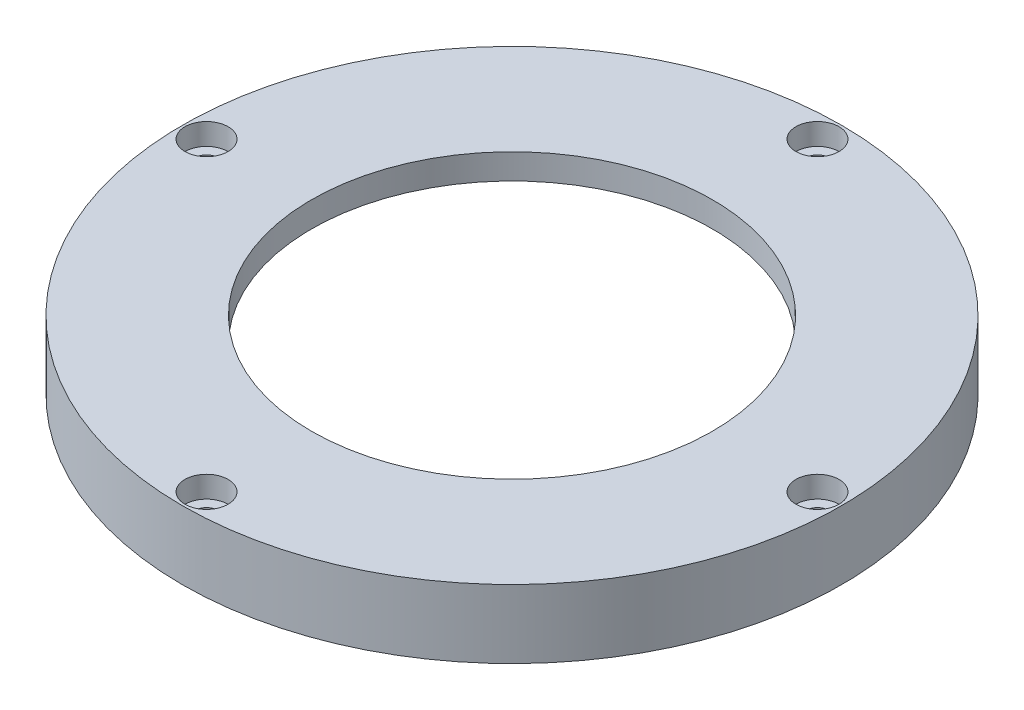
SolidWorks part; units mm, degrees
ref_plane "Front Plane" through (0, 0, 0) normal (0, 0, 1) x (1, 0, 0)
ref_plane "Top Plane" through (0, 0, 0) normal (0, 1, 0) x (1, 0, 0)
ref_plane "Right Plane" through (0, 0, 0) normal (1, 0, 0) x (0, 0, -1)
sketch "Sketch1" plane through (0, 0, 0) normal (0, 1, 0) x (1, 0, 0)
  line L0 (0, 0) -> (42.5, 0) construction
  circle A0 centre (0, 0) radius 45.85
  circle A1 centre (0, 0) radius 27.9
  circle A2 centre (42.5, 0) radius 1.5635
  circle A3 centre (0, -42.5) radius 1.5635
  circle A4 centre (-42.5, 0) radius 1.5635
  circle A5 centre (0, 0) radius 39.3
  circle A6 centre (0, 42.5) radius 1.5635
  point P13 (0, 0)
  dimension "D1" = 91.7
  dimension "D2" = 55.8
  dimension "D4" = 3.127
  dimension "D6" = 78.6
  dimension "D3" = 42.5
  dimension "D5" = 4
extrude "Boss-Extrude1" add sketch "Sketch1" against normal blind 6 contours A0 A5 A2 A4 A3 region at (-44.5532, 0, 0)
extrude "Boss-Extrude2" add sketch "Sketch1<4>" along normal blind 3.525 contours A1 A5 | A0 A5 A2 A4 A3 region at (-44.5532, 0, 0) region at (-38.1884, 0, 0)
sketch "Sketch1<4>" plane through (0, 0, 0) normal (0, 1, 0) x (1, 0, 0) same geometry as "Sketch1"
sketch "Sketch2" plane through (0, 3.525, 0) normal (0, 1, 0) x (1, 0, 0)
  circle A0 centre (42.5, 0) radius 3
  circle A1 centre (0, -42.5) radius 3
  circle A2 centre (-42.5, 0) radius 3
  circle A3 centre (0, 42.5) radius 3
  point P3 (0, 0)
  point P4 (-65.4034, -13.2807)
  point P5 (9.9433, -55.3007)
  point P6 (0, 0)
  point P9 (0, 0)
  point P17 (0, 0)
  dimension "D1" = 6
  dimension "D2" = 4
extrude "Cut-Extrude1" cut sketch "Sketch2" against normal blind 3
equation "\"bearing_21_OD\"= 21mm"
equation "\"pin_cirlce_diameter\"= 75mm"
equation "\"pin_diam\"= 6mm"
equation "\"gear_thickness\"= 4mm"
equation "\"ball_bearing_diam\"= 3.214mm"
equation "\"bearing_21_outer_clearance\"= 0.127mm'change this"
equation "\"bearing_15_OD\"= 15mm"
equation "\"bearing_15_outer_clearance\"= 0mm'change this"
equation "\"thrust_bearing_thickness\"= 5mm'measure this irl and change"
equation "\"D1@Boss-Extrude1\"=\"thrustBearingThickness\"+1mm"
equation "\"largeBearOD\"= 21mm"
equation "\"largeBearID\" = 15mm"
equation "\"largeBearOTight\"= 0.127mm'calibrate - hold onto gears"
equation "\"largeBearITight\"= 0mm'calibrate - hold onto eccentric nut"
equation "\"largeBearFlangeDiam\" = 22.5mm"
equation "\"largeBearFlangeWidth\" = 0.8mm"
equation "\"smallBearOD\"= 15mm"
equation "\"smallBearOTight\"= 0mm'calibrate - hold onto bottom of gearbox"
equation "\"smallBearOLoose\"= 0mm'calibrate - able to take off topHat"
equation "\"smallBearID\" = 10mm"
equation "\"smallBearITight\" = 0mm'hold onto "
equation "\"pinCircleDiam\"= 75mm"
equation "\"pinDiam\"= 6mm"
equation "\"sheetThickness\"= 0.1875in"
equation "\"ballBearDiam\"= 3.214mm"
equation "\"thrustBearingThickness\"= 5mm'measure this irl and change"
equation "\"thrustBearingID\"= 0mm'measure this irl and change"
equation "\"thrustBearingOD\"= 0mm'measure this irl and change"
equation "\"eccentricity\" = 1mm"
equation "\"D1@Boss-Extrude2\"=\"sheetThickness\"*2-(\"thrustBearingThickness\"+1)"
